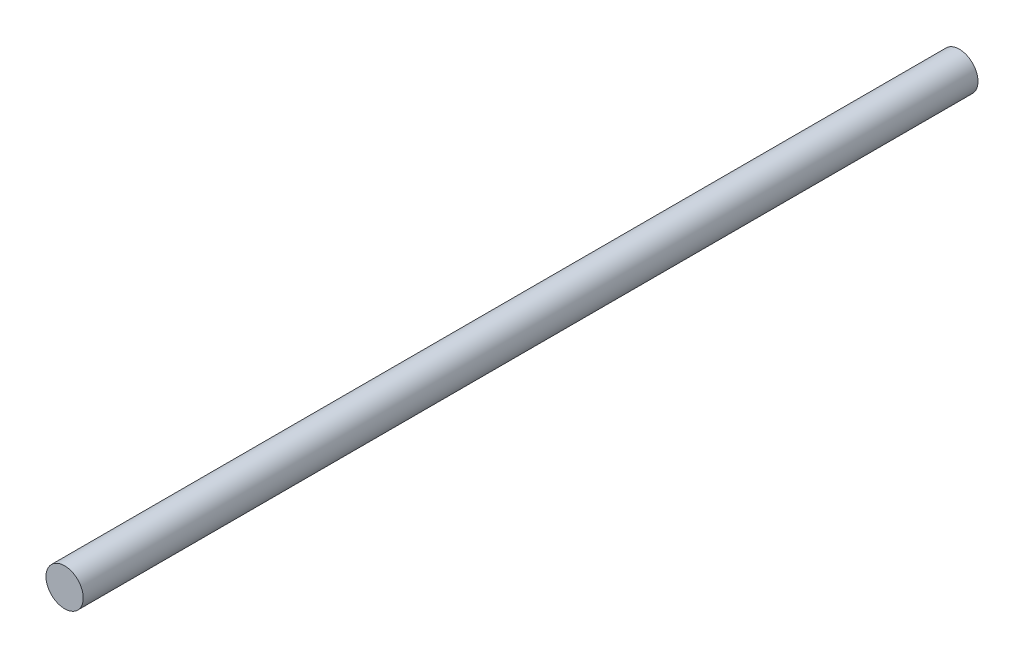
SolidWorks part; units mm, degrees
ref_plane "Front Plane" through (0, 0, 0) normal (0, 0, 1) x (1, 0, 0)
ref_plane "Top Plane" through (0, 0, 0) normal (0, 1, 0) x (1, 0, 0)
ref_plane "Right Plane" through (0, 0, 0) normal (1, 0, 0) x (0, 0, -1)
sketch "Sketch1" plane through (0, 0, 0) normal (0, 0, 1) x (1, 0, 0)
  circle A0 centre (0, 0) radius 1.25
extrude "Boss-Extrude1" add sketch "Sketch1" along normal blind 30 and the other way blind 30
